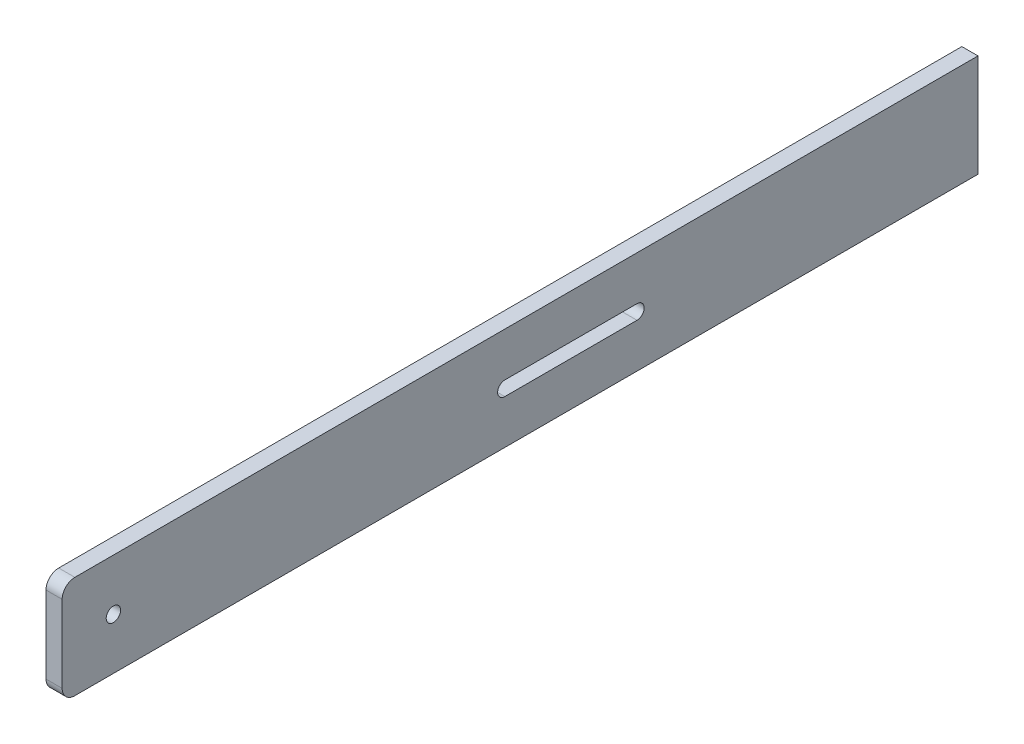
SolidWorks part; units mm, degrees
material "Maple"
ref_plane "Front Plane" through (0, 0, 0) normal (0, 0, 1) x (1, 0, 0)
ref_plane "Top Plane" through (0, 0, 0) normal (0, 1, 0) x (1, 0, 0)
ref_plane "Right Plane" through (0, 0, 0) normal (1, 0, 0) x (0, 0, -1)
sketch "Sketch1" plane through (0, 0, 0) normal (0, 0, 1) x (1, 0, 0)
  line L1 (-1.5875, 10.085) -> (1.5875, 10.085)
  line L2 (-1.5875, 10.085) -> (-1.5875, -10.085)
  line L3 (-1.5875, -10.085) -> (1.5875, -10.085)
  line L4 (1.5875, 10.085) -> (1.5875, -10.085)
  line L5 (-1.5875, 10.085) -> (1.5875, -10.085) construction
  line L6 (-1.5875, -10.085) -> (1.5875, 10.085) construction
  point P0 (0, 0)
  dimension "D1" = 20.17
  dimension "D2" = 3.175
extrude "Boss-Extrude1" add sketch "Sketch1" along normal blind 180.17
sketch "Sketch4" plane through (0, 0, 0) normal (1, 0, 0) x (0, 0, -1)
  line L0 (0, 0) -> (-80.085, 0) construction
  line L1 (-80.085, 0) -> (-80.085, -10.085) construction
  line L2 (-180.17, -10.085) -> (0, -10.085) construction
  dimension "D1" = 80.085
ref_axis "Axis4" through (0, -10.085, 80.085) along (0, 1, 0)
sketch "Sketch6" plane through (1.5875, 0, 0) normal (1, 0, 0) x (0, 0, -1)
  line L0 (-180.17, 0) -> (-170.085, 0) construction
  line L1 (-180.17, -10.085) -> (-180.17, 10.085) construction
  circle A0 centre (-170.085, 0) radius 1.415
  dimension "D2" = 2.83
  dimension "D1" = 10.085
extrude "Cut-Extrude1" cut sketch "Sketch6" against normal through all
fillet "Fillet1" radius 2.5 2 edges at (0, -10.085, 180.17) (0, 10.085, 180.17)
sketch "Sketch7" plane through (-1.5875, 0, 0) normal (-1, 0, 0) x (0, 0, 1)
  line L2 (0, 0) -> (80.085, 0) construction
  line L5 (80.085, -10.085) -> (80.085, 0) construction
  line L6 (80.085, 0) -> (80.085, 3.7337) construction
  line L9 (67.085, 0) -> (93.085, 0) construction
  line L10 (67.085, 1.415) -> (93.085, 1.415)
  line L11 (67.085, -1.415) -> (93.085, -1.415)
  arc A4 (67.085, 1.415) -> (67.085, -1.415) centre (67.085, 0) ccw
  arc A5 (93.085, -1.415) -> (93.085, 1.415) centre (93.085, 0) ccw
  point P5 (67.085, 0)
  point P7 (93.085, 0)
  point P10 (80.085, 0)
  dimension "D2" = 1.415
  dimension "D1" = 13
extrude "Cut-Extrude3" cut sketch "Sketch7" against normal blind 10
sketch "Sketch8" plane through (-1.5875, 0, 0) normal (-1, 0, 0) x (0, 0, 1)
  line L0 (80.085, 31.3179) -> (80.085, -31.3179) construction
  line L1 (80.085, -10.085) -> (80.085, 0) construction
  point P5 (80.085, 0)
ref_axis "Axis5" through (-1.5875, 31.3179, 80.085) along (0, -1, 0)
equation "\"length\"= 20mm"
equation "\"D1@Sketch1\"=\"length\" + 2*\"kerf\""
equation "\"width\"= 6.35 / 2"
equation "\"D2@Sketch1\"=\"width\" "
equation "\"depth\"=180"
equation "\"D1@Boss-Extrude1\"=\"depth\" + 2*\"kerf\""
equation "\"distance\"=80"
equation "\"D1@Sketch4\"=\"distance\" + \"kerf\""
equation "\"kerf\"= 0.17 / 2"
equation "\"D2@Sketch6\"=3 - 2*\"kerf\""
equation "\"D2@Sketch7\"=1.5 - \"kerf\""
equation "\"D1@Sketch6\"= 10.00mm + \"kerf\""
